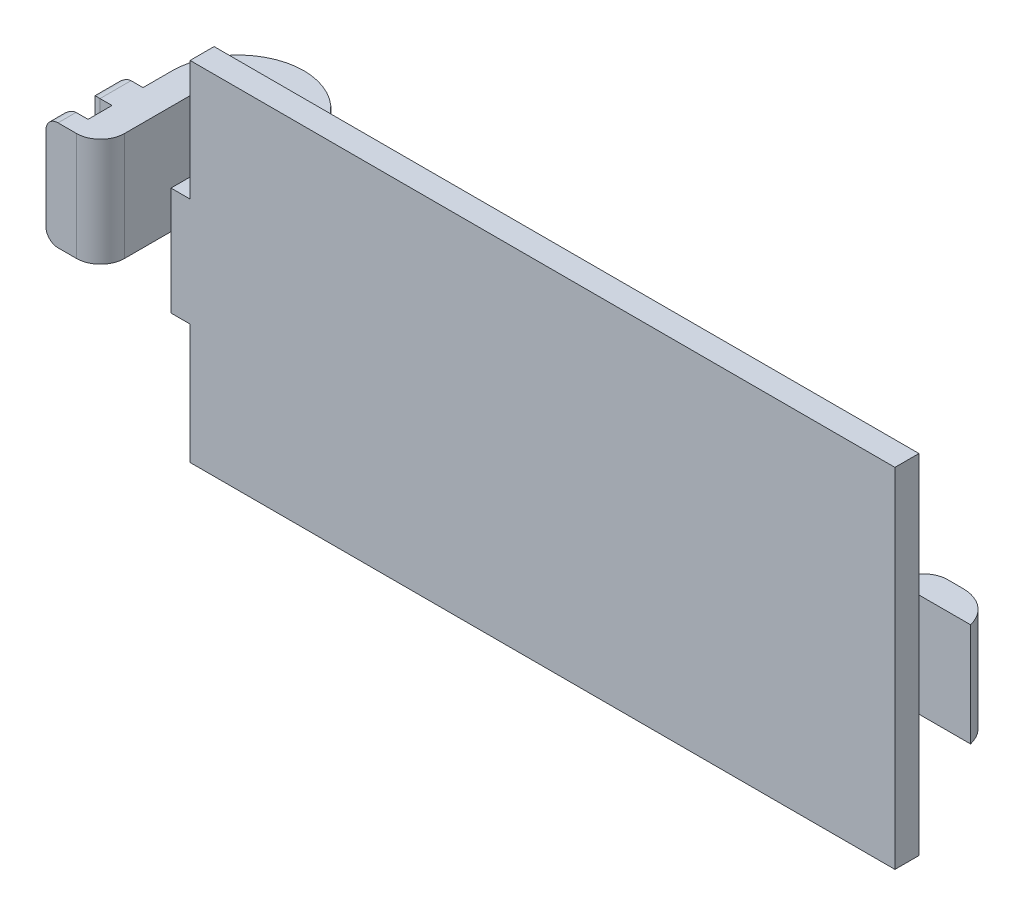
SolidWorks part; units mm, degrees
ref_plane "Front Plane" through (0, 0, 0) normal (0, 0, 1) x (1, 0, 0)
ref_plane "Top Plane" through (0, 0, 0) normal (0, 1, 0) x (1, 0, 0)
ref_plane "Right Plane" through (0, 0, 0) normal (1, 0, 0) x (0, 0, -1)
other "Graphic1"
other "Imported Graphic (Open) -1"
other "Imported Graphic (Closed) -2"
sketch "Sketch1" plane through (0, 0, 0) normal (0, 0, 1) x (1, 0, 0)
  line L0 (-13.4493, -14.4974) -> (45.2507, -14.4974)
  line L1 (-13.4493, 0.0026) -> (45.2507, 0.0026)
  line L2 (-13.4493, -14.4974) -> (-13.4493, 14.5026)
  line L3 (-13.4493, 14.5026) -> (45.2507, 14.5026)
  line L4 (45.2507, -14.4974) -> (45.2507, 14.5026)
  dimension "D1" = 14.5
extrude "Boss-Extrude1" add sketch "Sketch1" along normal blind 2 contours L0 L4 L1 L2 | L1 L4 L3 L2
sketch "Sketch2" plane through (0, 0, 2) normal (0, 0, 1) x (1, 0, 0)
  line L0 (45.2507, -14.4974) -> (45.2507, 14.5026) construction
  line L1 (43.3431, 0) -> (45.2507, 0)
  line L2 (43.3431, -4.3) -> (43.3431, 4.3)
  line L3 (43.3431, 4.3) -> (45.2507, 4.3)
  line L4 (45.2507, -4.3) -> (45.2507, 4.3)
  line L5 (43.3431, -4.3) -> (45.2507, -4.3)
  dimension "D1" = 4.3
extrude "Boss-Extrude2" add sketch "Sketch2" against normal blind 4.3 contours L2 L3 L4 L5
sketch "Sketch3" plane through (45.2507, 0, 0) normal (1, 0, 0) x (0, 0, -1)
  line L1 (0, 4.3) -> (2.3, 4.3)
  line L2 (0, 4.3) -> (0, -4.3)
  line L3 (0, -4.3) -> (2.3, -4.3)
  line L4 (2.3, 4.3) -> (2.3, -4.3)
extrude "Boss-Extrude3" add sketch "Sketch3" along normal blind 4.3
fillet "Fillet3" radius 2 1 edges at (43.3431, 0, -2.3)
sketch "Sketch4" plane through (0, 0, 0) normal (0, 0, -1) x (-1, 0, 0)
  line L0 (13.4493, -14.4974) -> (13.4493, 14.5026) construction
  line L1 (12.4996, 4.5026) -> (13.4493, 4.5026)
  line L2 (12.4996, 4.5026) -> (12.4996, -4.4974)
  line L3 (12.4996, -4.4974) -> (13.4493, -4.4974)
  line L4 (13.4493, 4.5026) -> (13.4493, -4.4974)
  dimension "D1" = 10
  dimension "D2" = 10
extrude "Boss-Extrude4" add sketch "Sketch4" along normal blind 12 contours L2 L3 L4 L1
sketch "Sketch5" plane through (-13.4493, 0, 0) normal (-1, 0, 0) x (0, 0, 1)
  line L0 (2, -14.4974) -> (2, 14.5026) construction
  line L1 (-12, 4.5026) -> (2, 4.5026)
  line L2 (-12, 4.5026) -> (-12, -4.5144)
  line L3 (-12, -4.5144) -> (2, -4.5144)
  line L4 (2, 4.5026) -> (2, -4.5144)
extrude "Boss-Extrude5" add sketch "Sketch5" along normal blind 10
sketch "Sketch6" plane through (0, 4.5026, 0) normal (0, 1, 0) x (1, 0, 0)
fillet "Fillet4" radius 5.5 2 edges at (-23.4493, -0.0059, -12) (-12.4996, 0.0026, -12)
sketch "Sketch7" plane through (0, 4.5026, 0) normal (0, 1, 0) x (1, 0, 0)
  line L0 (-17.9745, 11.9999) -> (-17.9745, -2.5421) construction
  line L1 (-12.4996, 6.5) -> (-23.4493, 6.5) construction
  line L2 (-23.4493, -2) -> (-13.4493, -2) construction
  line L3 (-20.9096, 6.5) -> (-15.0393, 6.5)
  line L4 (-20.9096, 6.5) -> (-20.9096, -2)
  line L5 (-20.9096, -2) -> (-15.0393, -2)
  line L6 (-15.0393, 6.5) -> (-15.0393, -2)
  circle A0 centre (-17.9745, 6.5) radius 2.9351
  line M4 (-23.4493, -2) -> (-13.4493, -2)
extrude "Cut-Extrude1" cut sketch "Sketch7" against normal blind 12 contours L3 A0 | L3 A0 | A0 L4 L6 M4
sketch "Sketch8" plane through (-23.4493, 0, 0) normal (-1, 0, 0) x (0, 0, 1)
  line L0 (2, 4.5026) -> (-6.5, 4.5026) construction
  line L1 (-4.0801, 4.5026) -> (-1.5, 4.5026)
  line L2 (-4.0801, 4.5026) -> (-4.0801, -4.5144)
  line L3 (-4.0801, -4.5144) -> (-1.5, -4.5144)
  line L4 (-1.5, 4.5026) -> (-1.5, -4.5144)
  line L5 (-6.5, -4.5144) -> (2, -4.5144) construction
  line L6 (2, 4.5026) -> (0, 4.5026) construction
  line L7 (2, -4.5144) -> (0.5, -4.5144)
  line L8 (2, -4.5144) -> (2, 4.5026)
  line L9 (2, 4.5026) -> (0.5, 4.5026)
  line L10 (0.5, -4.5144) -> (0.5, 4.5026)
  dimension "D1" = 3.5
  dimension "D2" = 1.5
extrude "Boss-Extrude6" add sketch "Sketch8" along normal blind 2
sketch "Sketch9" plane through (0, 0, 0) normal (0, 0, -1) x (-1, 0, 0)
  line L0 (12.5106, -2.7463) -> (10.5897, -2.7463)
  line L1 (12.4996, 4.5026) -> (10.5787, 4.5026)
  line L2 (12.4996, 4.5026) -> (12.4996, 2.8168)
  line L3 (12.4996, 2.8168) -> (10.5787, 2.8168)
  line L4 (10.5787, 4.5026) -> (10.5787, 2.8168)
  line L5 (12.5106, -2.7463) -> (12.5106, -4.4321)
  line L6 (12.5106, -4.4321) -> (10.5897, -4.4321)
  line L7 (10.5897, -2.7463) -> (10.5897, -4.4321)
sketch "Sketch10" plane through (0, 0, 0) normal (0, 0, -1) x (-1, 0, 0)
extrude "Boss-Extrude7" add sketch "Sketch9" along normal blind 3
fillet "Fillet6" radius 3 2 edges at (-10.5897, -3.5892, -3) (-10.5787, 3.6597, -3)
sketch "Sketch11" plane through (0, 0, 0) normal (0, 0, -1) x (-1, 0, 0)
  line L0 (13.4493, 4.5026) -> (13.4493, 14.5026) construction
  line L5 (13.0062, 9.9367) -> (13.4493, 9.9367)
  line L7 (13.0062, 6.6896) -> (13.4493, 6.6896)
  line L8 (13.4493, 9.9367) -> (13.4493, 6.6896)
fillet "Fillet9" radius 3 1 edges at (49.5507, 0, -2.3)
fillet "Fillet11" radius 1 4 edges at (-25.4493, 4.5026, -2.7901) (-25.4493, -0.0059, -1.5) (-25.4493, -4.5144, -2.7901) (-25.4493, -0.0059, -4.0801)
fillet "Fillet12" radius 1 3 edges at (-25.4493, -4.5144, 1.25) (-25.4493, 4.5026, 1.25) (-25.4493, -0.0059, 0.5)
fillet "Fillet13" radius 2 1 edges at (-20.9096, -0.0059, 2)
